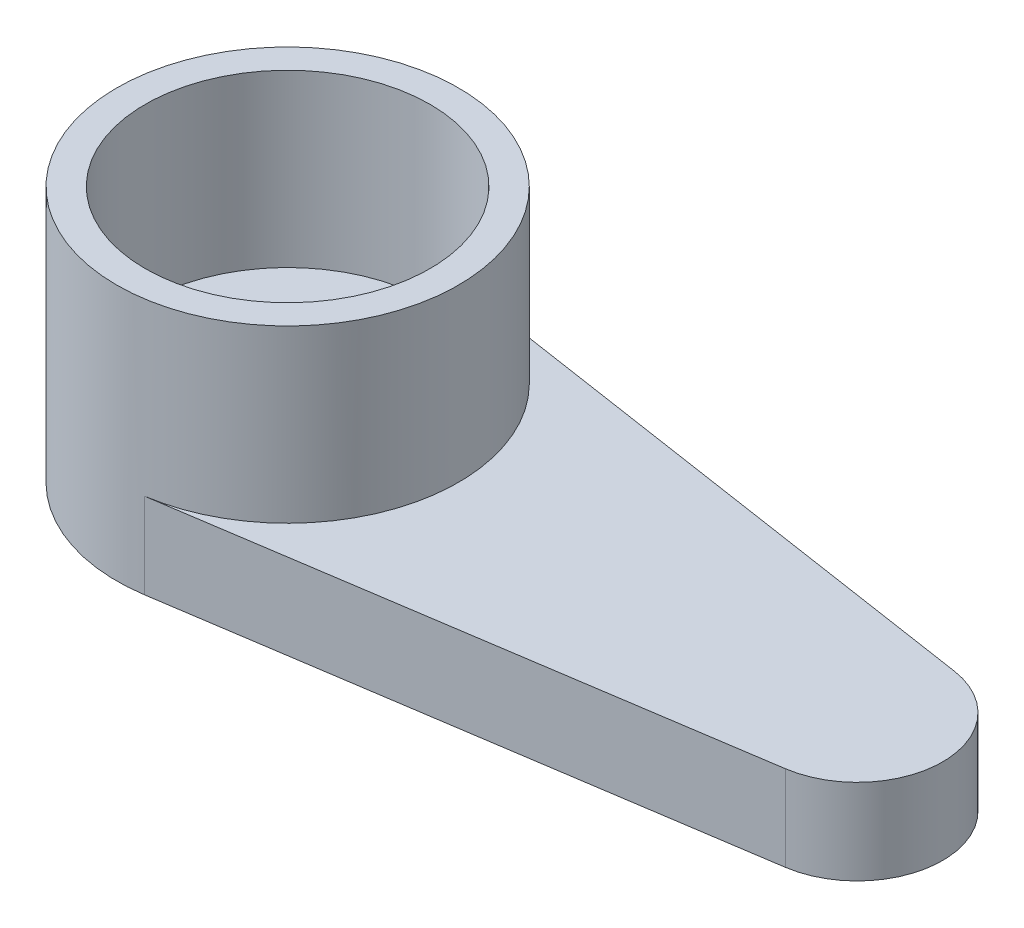
SolidWorks part; units mm, degrees
ref_plane "Front Plane" through (0, 0, 0) normal (0, 0, 1) x (1, 0, 0)
ref_plane "Top Plane" through (0, 0, 0) normal (0, 1, 0) x (1, 0, 0)
ref_plane "Right Plane" through (0, 0, 0) normal (1, 0, 0) x (0, 0, -1)
sketch "Sketch1" plane through (0, 0, 0) normal (0, 1, 0) x (1, 0, 0)
  line L0 (0.45, 2.9661) -> (10.225, 1.483)
  line L3 (10.225, -1.483) -> (0.45, -2.9661)
  arc A0 (0.45, 2.9661) -> (0.45, -2.9661) centre (0, 0) ccw
  arc A1 (10.225, -1.483) -> (10.225, 1.483) centre (10, 0) ccw
  circle A2 centre (0, 0) radius 1.5
  point P6 (20.4576, -1.4285)
  dimension "D2" = 3
  dimension "D3" = 6
  dimension "D4" = 3
  dimension "D1" = 10
extrude "Boss-Extrude1" add sketch "Sketch1" along normal blind 1.5
sketch "Sketch2" plane through (0, 1.5, 0) normal (0, 1, 0) x (1, 0, 0)
  line L0 (10.225, 1.483) -> (0.45, 2.9661) construction
  circle A0 centre (0, 0) radius 3
  circle A1 centre (0, 0) radius 2.5
  dimension "D1" = 5
extrude "Boss-Extrude2" add sketch "Sketch2" along normal blind 3
